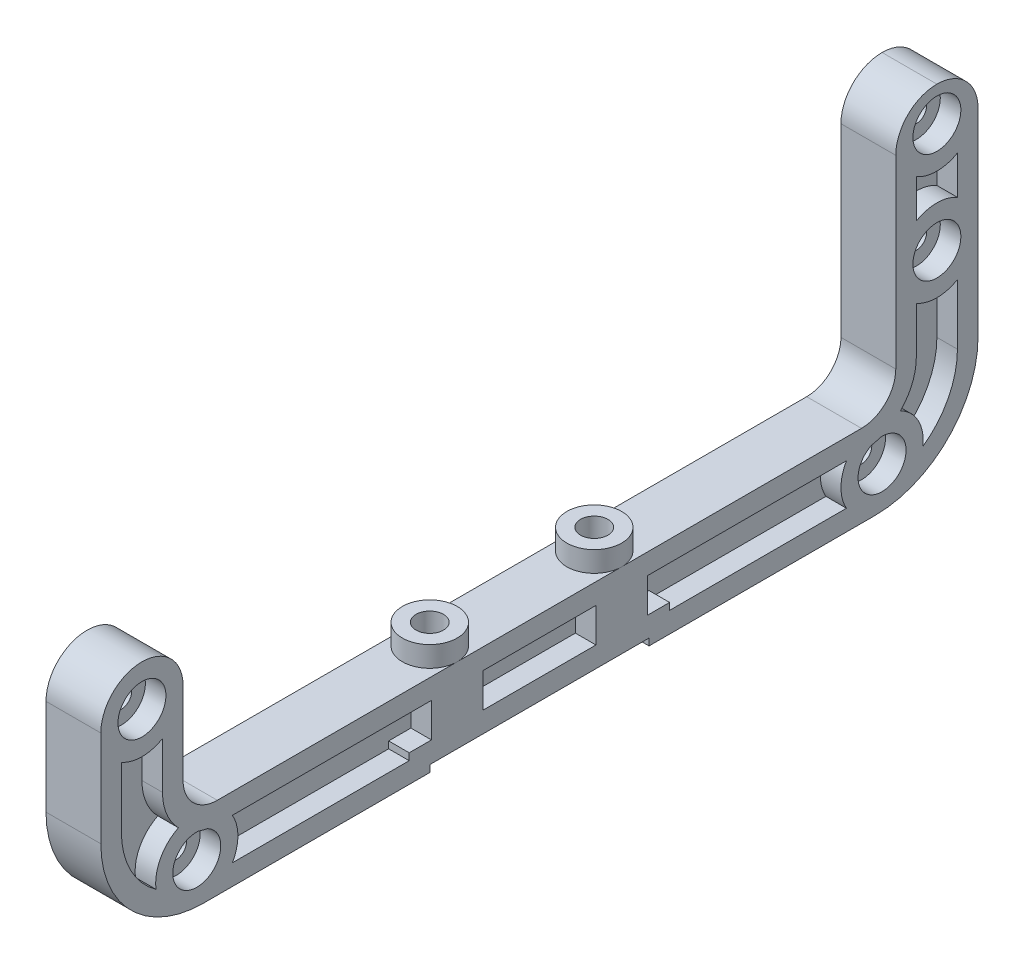
SolidWorks part; units mm, degrees
material "ABS"
ref_plane "Front Plane" through (0, 0, 0) normal (0, 0, 1) x (1, 0, 0)
ref_plane "Top Plane" through (0, 0, 0) normal (0, 1, 0) x (1, 0, 0)
ref_plane "Right Plane" through (0, 0, 0) normal (1, 0, 0) x (0, 0, -1)
sketch "Sketch1" plane through (0, 0, 0) normal (1, 0, 0) x (0, 0, -1)
  line L0 (34, 44) -> (34, 23) construction
  line L1 (-40, -6) -> (40, -6)
  line L2 (-40, -6) -> (-40, 6)
  line L3 (-40, 6) -> (40, 6)
  line L4 (40, -6) -> (40, 6)
  line L5 (-40, -6) -> (40, 6) construction
  line L6 (-40, 6) -> (40, -6) construction
  line L7 (40, 6) -> (28, 6)
  line L8 (40, 6) -> (40, 44)
  line L9 (40, 44) -> (28, 44)
  line L10 (28, 6) -> (28, 44)
  line L11 (-40, -6) -> (-8, -6)
  line L12 (-40, -6) -> (-40, -5)
  line L13 (-40, -5) -> (-8, -5)
  line L14 (-8, -6) -> (-8, -5)
  line L15 (-24, -5) -> (-24, 6) construction
  line L16 (-8, -5) -> (-8, 6)
  line L17 (-24, 6) -> (-24, 44) construction
  line L23 (-40, -5) -> (-40, 6)
  line L27 (-88, 44) -> (-76, 44)
  line L28 (-76, 6) -> (-76, 44)
  line L29 (-88, 6) -> (-76, 6)
  line L30 (-88, 6) -> (-88, 44)
  line L31 (-8, 6) -> (-88, 6)
  line L32 (-88, -6) -> (-88, 6)
  line L33 (-8, -6) -> (-88, -6)
  line L34 (-8, -6) -> (-8, 6)
  circle A0 centre (34, 39) radius 1.5
  circle A1 centre (34, 23) radius 1.5
  circle A2 centre (26, 0) radius 1.5
  circle A9 centre (-74, 0) radius 1.5
  circle A10 centre (-82, 39) radius 1.5
  circle A11 centre (-82, 23) radius 1.5
  point P0 (0, 0)
  dimension "D7" = 3
  dimension "D8" = 3
  dimension "D9" = 3
  dimension "D10" = 16
  dimension "D11" = 5
  dimension "D12" = 8
  dimension "D13" = 6
  dimension "D14" = 6
  dimension "D1" = 12
  dimension "D2" = 12
  dimension "D3" = 80
  dimension "D4" = 50
  dimension "D5" = 1
  dimension "D6" = 32
extrude "Boss-Extrude1" add sketch "Sketch1" along normal blind 8 contours L14 L1 L4 L3 L2 L13 A2 | L10 L3 L8 L9 A1 A0 | L13 L16 L3 L2 | L2 | A11 | A10 | L30 L27 L28 L29 region at (0, 0, 63.8758) region at (0, 0, -15.8758) region at (0, 0.5, 24) region at (0, 24.808, -34) region at (0, 39, 82) region at (0, 23, 82)
fillet "Fillet1" radius 6 2 edges at (4, 44, -28) (4, 44, -40)
fillet "Fillet2" radius 15 1 edges at (4, -6, -40)
fillet "Fillet3" radius 5 1 edges at (4, 6, -28)
sketch "Sketch2" plane through (0, 6, 0) normal (0, 1, 0) x (1, 0, 0)
  line L0 (4, -12) -> (4, -36) construction
  line L1 (4, -36) -> (4, -40) construction
  line L2 (8, -40) -> (0, -40) construction
  circle A0 centre (4, -36) radius 2
  circle A1 centre (4, -12) radius 2
  dimension "D1" = 4
  dimension "D2" = 4
  dimension "D3" = 4
  dimension "D4" = 24
extrude "Cut-Extrude1" cut sketch "Sketch2" against normal through all
sketch "Sketch3" plane through (0, 6, 0) normal (0, 1, 0) x (1, 0, 0)
  circle A0 centre (4, -12) radius 4
  circle A1 centre (4, -36) radius 4
  circle A4 centre (4, -12) radius 2
  circle A5 centre (4, -12) radius 2
  circle A7 centre (4, -36) radius 2
  circle A8 centre (4, -36) radius 2
  dimension "D1" = 8
  dimension "D2" = 8
  dimension "D3" = 0
  dimension "D4" = 0
extrude "Boss-Extrude2" add sketch "Sketch3" along normal blind 3
sketch "Sketch4" plane through (8, 0, 0) normal (1, 0, 0) x (0, 0, -1)
  line L9 (-8, 6) -> (-8, 9) construction
  line L10 (-15.75, -2) -> (-8.25, -2)
  line L11 (-15.75, -2) -> (-15.75, 3)
  line L12 (-15.75, 3) -> (-8.25, 3)
  line L13 (-8.25, -2) -> (-8.25, 3)
  line L14 (-15.75, -2) -> (-8.25, 3) construction
  line L15 (-15.75, 3) -> (-8.25, -2) construction
  line L16 (-30.25, 3) -> (-35, 3)
  line L17 (-30.25, 3) -> (-30.25, -2)
  line L18 (-5, -3) -> (25, -3)
  line L19 (37, 9) -> (37, 38)
  line L20 (31, 38) -> (31, 11)
  line L21 (23, 3) -> (-12, 3)
  line L24 (-36, 3) -> (-79, 3)
  line L25 (-36, 3) -> (-79, 3)
  line L26 (-5, -2) -> (-5, -3)
  line L27 (-5, -3) -> (25, -3)
  line L28 (37, 9) -> (37, 38)
  line L29 (31, 38) -> (31, 11)
  line L30 (23, 3) -> (-12, 3)
  line L35 (-5, -2) -> (-5, -3)
  line L36 (-30.25, -2) -> (-35, -2)
  line L37 (-35, 3) -> (-35, -2)
  line L38 (-12, 3) -> (-36, 3)
  line L39 (-12, 3) -> (-36, 3)
  line L40 (-43, -3) -> (-43, -2)
  line L41 (-43, -3) -> (-43, -2)
  line L42 (-43, -2) -> (-5, -2)
  line L43 (-43, -2) -> (-5, -2)
  line L44 (-85, 41) -> (-85, -3)
  line L48 (-85, 41) -> (-85, -3)
  line L50 (-85, -3) -> (-43, -3)
  line L54 (-85, -3) -> (-43, -3)
  line L59 (-79, 3) -> (-79, 41)
  line L60 (-79, 3) -> (-79, 41)
  line L61 (-79, 41) -> (-85, 41)
  line L62 (-79, 41) -> (-85, 41)
  circle A0 centre (34, 39) radius 3.5
  circle A1 centre (34, 23) radius 3.5
  circle A2 centre (26, 0) radius 3.5
  circle A7 centre (26, 0) radius 6
  circle A8 centre (34, 23) radius 6
  circle A9 centre (34, 39) radius 6
  arc A11 (25, -3) -> (37, 9) centre (25, 9) ccw
  arc A12 (37, 38) -> (34, 41) centre (34, 38) ccw
  arc A13 (34, 41) -> (31, 38) centre (34, 38) ccw
  arc A14 (23, 3) -> (31, 11) centre (23, 11) ccw
  arc A15 (25, -3) -> (37, 9) centre (25, 9) ccw
  arc A16 (37, 38) -> (34, 41) centre (34, 38) ccw
  arc A17 (34, 41) -> (31, 38) centre (34, 38) ccw
  arc A18 (23, 3) -> (31, 11) centre (23, 11) ccw
  point P9 (-12, 0.5)
  circle M18 centre (26, 0) radius 1.5
  circle M32 centre (34, 23) radius 1.5
  circle M33 centre (34, 39) radius 1.5
  dimension "D1" = 7
  dimension "D2" = 7
  dimension "D3" = 7
  dimension "D9" = 12
  dimension "D10" = 12
  dimension "D11" = 12
  dimension "D6" = 7.5
  dimension "D7" = 4
  dimension "D4" = 3
extrude "Cut-Extrude2" cut sketch "Sketch4" against normal blind 3 contours A7 L30 L13 L43 L35 L27 | L17 L43 L11 L39 | A18 A7 A15 L28 A8 | A9 L29 A8 L28 | A16 A17 L29 A0 L28 M33 | A17 A16 L28 A0 L29 | L28 A1 L29 M32 | L28 A1 | L29 A1 | A18 A2 L27 A15 M18 | A15 L27 A2 region at (8, 0.5, 23) region at (8, 0.0484, -6.2508) region at (8, 9.3623, -33.6116) region at (8, 3.1897, -25.1301) region at (8, -3.1103, -26.3549) region at (8, 23, -30.7987) region at (8, 23, -31.0922) region at (8, 31, -34) region at (8, 23, -37.2013) region at (8, 42.2881, -33.0881) region at (8, 37.5986, -31.0814)
ref_plane "Plane1" through (4, 0, 0) normal (-1, 0, 0) x (0, 0, 1)
mirror "Mirror1" about plane through (4, 0, 0) normal (-1, 0, 0) of "Cut-Extrude2"
ref_plane "Plane3" through (0, 0, 24) normal (0, 0, -1) x (-1, 0, 0)
mirror "Mirror2" about plane through (0, 0, 24) normal (0, 0, -1) of "Cut-Extrude2"
ref_plane "Plane4" through (4, 0, 0) normal (-1, 0, 0) x (0, 0, 1)
mirror "Mirror3" about plane through (4, 0, 0) normal (-1, 0, 0) of "Mirror2"
fillet "Fillet4" radius 5 1 edges at (4, 6, 76)
fillet "Fillet5" radius 15 1 edges at (4, -6, 88)
fillet "Fillet6" radius 6 2 edges at (4, 44, 76) (4, 44, 88)
sketch "Sketch5" plane through (0, 0, 0) normal (-1, 0, 0) x (0, 0, 1)
  line L24 (76, 38) -> (76, 11)
  line L25 (71, 6) -> (36, 6)
  line L26 (36, 6) -> (12, 6)
  line L27 (12, 6) -> (-23, 6)
  line L28 (-28, 11) -> (-28, 38)
  line L29 (-40, 38) -> (-40, 9)
  line L30 (-25, -6) -> (8, -6)
  line L31 (8, -6) -> (8, -5)
  line L32 (8, -5) -> (40, -5)
  line L33 (40, -5) -> (40, -6)
  line L34 (40, -6) -> (73, -6)
  line L35 (88, 9) -> (88, 38)
  line L36 (76, 38) -> (76, 11)
  line L37 (71, 6) -> (36, 6)
  line L38 (36, 6) -> (12, 6)
  line L39 (12, 6) -> (-23, 6)
  line L40 (-28, 11) -> (-28, 38)
  line L41 (-40, 38) -> (-40, 9)
  line L42 (-25, -6) -> (8, -6)
  line L43 (8, -6) -> (8, -5)
  line L44 (8, -5) -> (40, -5)
  line L45 (40, -5) -> (40, -6)
  line L46 (40, -6) -> (73, -6)
  line L47 (88, 9) -> (88, 38)
  circle A8 centre (82, 23) radius 6
  arc A16 (88, 38) -> (82, 44) centre (82, 38) ccw
  arc A17 (82, 44) -> (76, 38) centre (82, 38) ccw
  arc A18 (71, 6) -> (76, 11) centre (71, 11) ccw
  arc A19 (-28, 11) -> (-23, 6) centre (-23, 11) ccw
  arc A20 (-28, 38) -> (-34, 44) centre (-34, 38) ccw
  arc A21 (-34, 44) -> (-40, 38) centre (-34, 38) ccw
  arc A22 (-40, 9) -> (-25, -6) centre (-25, 9) ccw
  arc A23 (73, -6) -> (88, 9) centre (73, 9) ccw
  arc A24 (88, 38) -> (82, 44) centre (82, 38) ccw
  arc A25 (82, 44) -> (76, 38) centre (82, 38) ccw
  arc A26 (71, 6) -> (76, 11) centre (71, 11) ccw
  arc A27 (-28, 11) -> (-23, 6) centre (-23, 11) ccw
  arc A28 (-28, 38) -> (-34, 44) centre (-34, 38) ccw
  arc A29 (-34, 44) -> (-40, 38) centre (-34, 38) ccw
  arc A30 (-40, 9) -> (-25, -6) centre (-25, 9) ccw
  arc A31 (73, -6) -> (88, 9) centre (73, 9) ccw
  dimension "D1" = 0
extrude "Cut-Extrude3" cut sketch "Sketch5" against normal through all contours A24 A25 L36 A8 L47 region at (0, 35.2124, 82) body kept at (0, 23, 88)
